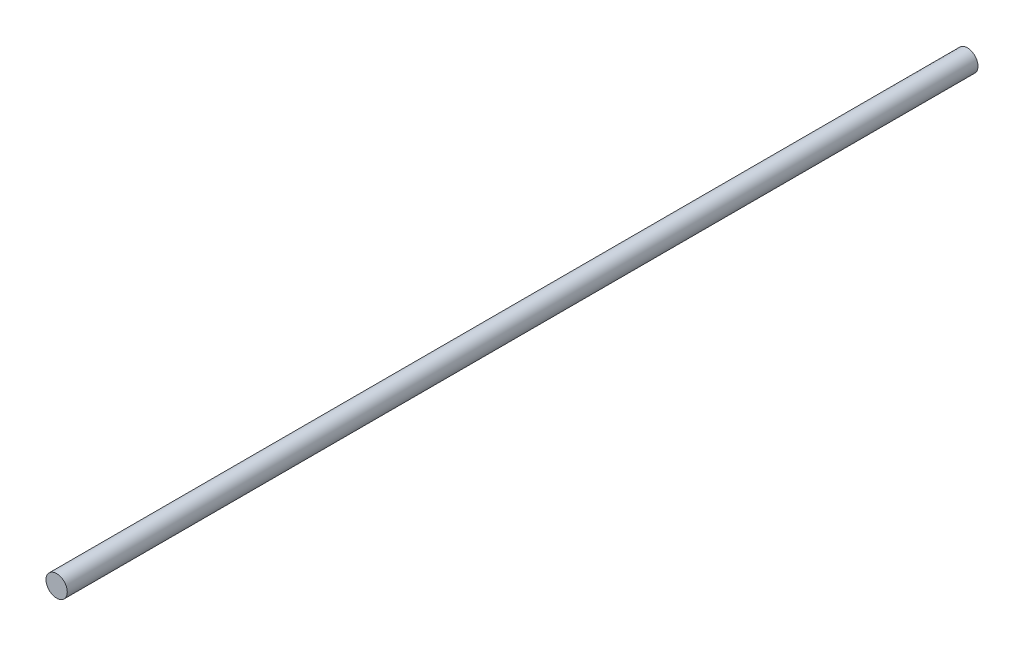
SolidWorks part; units mm, degrees
ref_plane "Plano frontal" through (0, 0, 0) normal (0, 0, 1) x (1, 0, 0)
ref_plane "Plano superior" through (0, 0, 0) normal (0, 1, 0) x (1, 0, 0)
ref_plane "Plano direito" through (0, 0, 0) normal (1, 0, 0) x (0, 0, -1)
sketch "Esboço1" plane through (0, 0, 0) normal (0, 0, 1) x (1, 0, 0)
  circle A0 centre (0, 0) radius 4
  dimension "D1" = 8
extrude "Ressalto-extrusão1" add sketch "Esboço1" along normal mid plane 342
